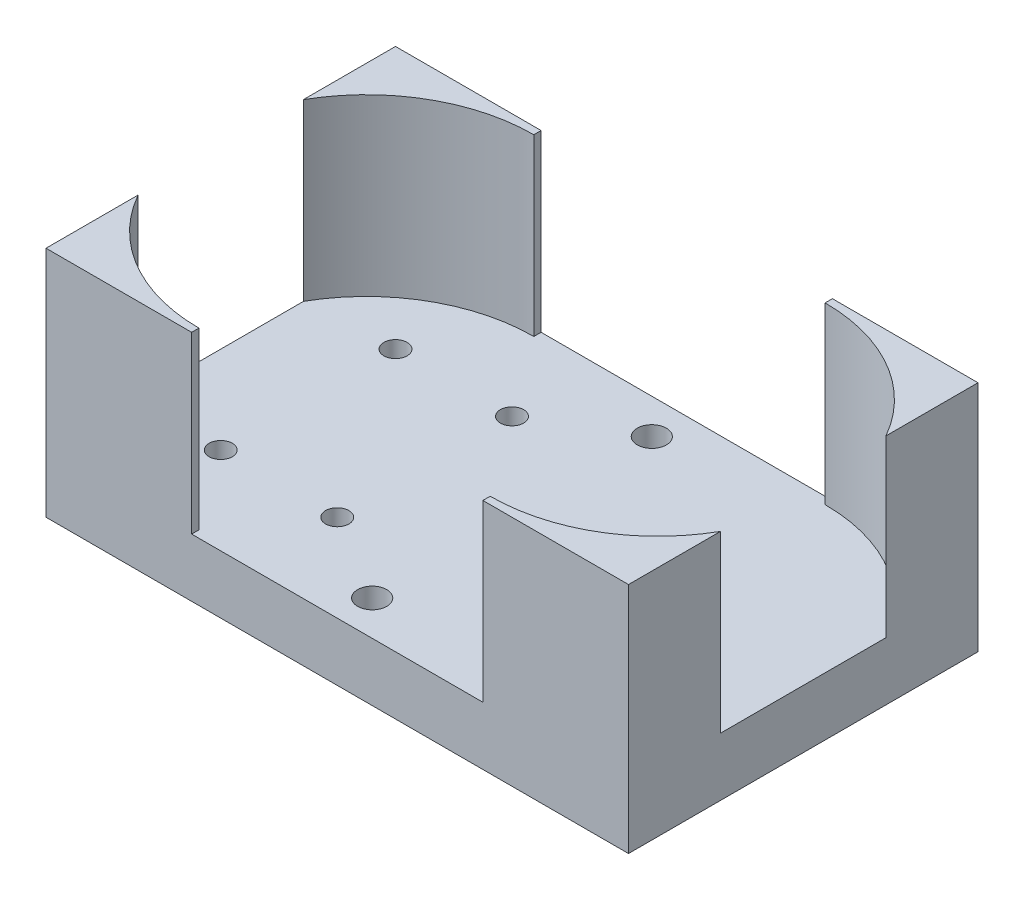
SolidWorks part; units mm, degrees
ref_plane "前视基准面" through (0, 0, 0) normal (0, 0, 1) x (1, 0, 0)
ref_plane "上视基准面" through (0, 0, 0) normal (0, 1, 0) x (1, 0, 0)
ref_plane "右视基准面" through (0, 0, 0) normal (1, 0, 0) x (0, 0, -1)
other "Configuration Table"
sketch "草图1" plane through (0, 0, 0) normal (0, 1, 0) x (1, 0, 0)
  line L5 (0, 0) -> (20, 0)
  line L6 (0, 0) -> (0, 12)
  line L11 (0, 12) -> (20, 12)
  line L12 (20, 0) -> (20, 12)
  dimension "D1" = 20
  dimension "D2" = 12
extrude "凸台-拉伸1" add sketch "草图1" along normal blind 2
sketch "草图2" plane through (0, 2, 0) normal (0, 1, 0) x (1, 0, 0)
  line L0 (20, 12) -> (0, 12) construction
  line L1 (0, 12) -> (0, 0) construction
  line L2 (20, 0) -> (20, 12) construction
  circle A0 centre (15, 6) radius 2
  circle A1 centre (5, 6) radius 3.5
  dimension "D1" = 4
  dimension "D2" = 7
  dimension "D3" = 6
  dimension "D4" = 5
  dimension "D5" = 5
sketch "草图4" plane through (0, 2, 0) normal (0, 1, 0) x (1, 0, 0)
  line L0 (20, 12) -> (0, 12) construction
  line L1 (15, 12) -> (5, 12)
  line L2 (15, 12) -> (15, 0)
  line L3 (15, 0) -> (5, 0)
  line L4 (5, 12) -> (5, 0)
  line L5 (0, 0) -> (20, 0) construction
  line L7 (5, 12) -> (0, 12)
  line L8 (5, 12) -> (5, 0)
  line L9 (5, 0) -> (0, 0)
  line L10 (0, 12) -> (0, 0)
  line L11 (20, 0) -> (15, 0)
  line L12 (20, 0) -> (20, 12)
  line L13 (20, 12) -> (15, 12)
  line L14 (15, 0) -> (15, 12)
  circle A0 centre (15, 6) radius 5.75
  circle A1 centre (5, 6) radius 5.75
  line M8 (0, 12) -> (0, 0)
  line M9 (0, 0) -> (20, 0)
  line M10 (20, 0) -> (20, 12)
  line M11 (20, 12) -> (0, 12)
  dimension "D1" = 11.5
  dimension "D2" = 0
  dimension "D3" = 0
extrude "凸台-拉伸2" add sketch "草图4" along normal blind 6 contours A1 L8 M11 M8 | A1 L8 M8 M9 | A0 L14 M10 M11 | A0 L14 M9 M10 region at (18.5199, 2, -11.1492) region at (1.4801, 2, -11.1492) region at (18.5199, 2, -0.8508) region at (1.4801, 2, -0.8508)
sketch "草图5" plane through (0, 0, 0) normal (0, -1, 0) x (1, 0, 0)
  line L0 (10, 0) -> (10, -12) construction
  line L1 (0, 0) -> (20, 0) construction
  line L2 (20, -12) -> (0, -12) construction
  circle A0 centre (10, -1.2) radius 0.5
  circle A1 centre (10, -10.8) radius 0.5
  circle A2 centre (10, -1.2) radius 1
  circle A3 centre (10, -10.8) radius 1
  dimension "D1" = 1
  dimension "D2" = 2
  dimension "D3" = 1.2
  dimension "D4" = 1.2
extrude "切除-拉伸1" cut sketch "草图5" against normal through all contours A1 | A0
extrude "切除-拉伸2" cut sketch "草图5<3>" against normal offset from surface (1 mm away) 1 contours A3 | A2 up to face at (10, 2, -11.3)
sketch "草图5<3>" plane through (0, 0, 0) normal (0, -1, 0) x (1, 0, 0) same geometry as "草图5"
sketch "草图6" plane through (0, 0, 0) normal (0, -1, 0) x (1, 0, 0)
  line L0 (0, -12) -> (0, 0) construction
  line L1 (0, 0) -> (20, 0) construction
  line L2 (20, -12) -> (0, -12) construction
  circle A0 centre (3, -3) radius 0.4
  circle A1 centre (3, -9) radius 0.4
  circle A2 centre (7, -9) radius 0.4
  circle A3 centre (7, -3) radius 0.4
  dimension "D1" = 0.8
  dimension "D2" = 3
  dimension "D3" = 3
  dimension "D4" = 3
  dimension "D5" = 7
extrude "切除-拉伸3" cut sketch "草图6" against normal through all
